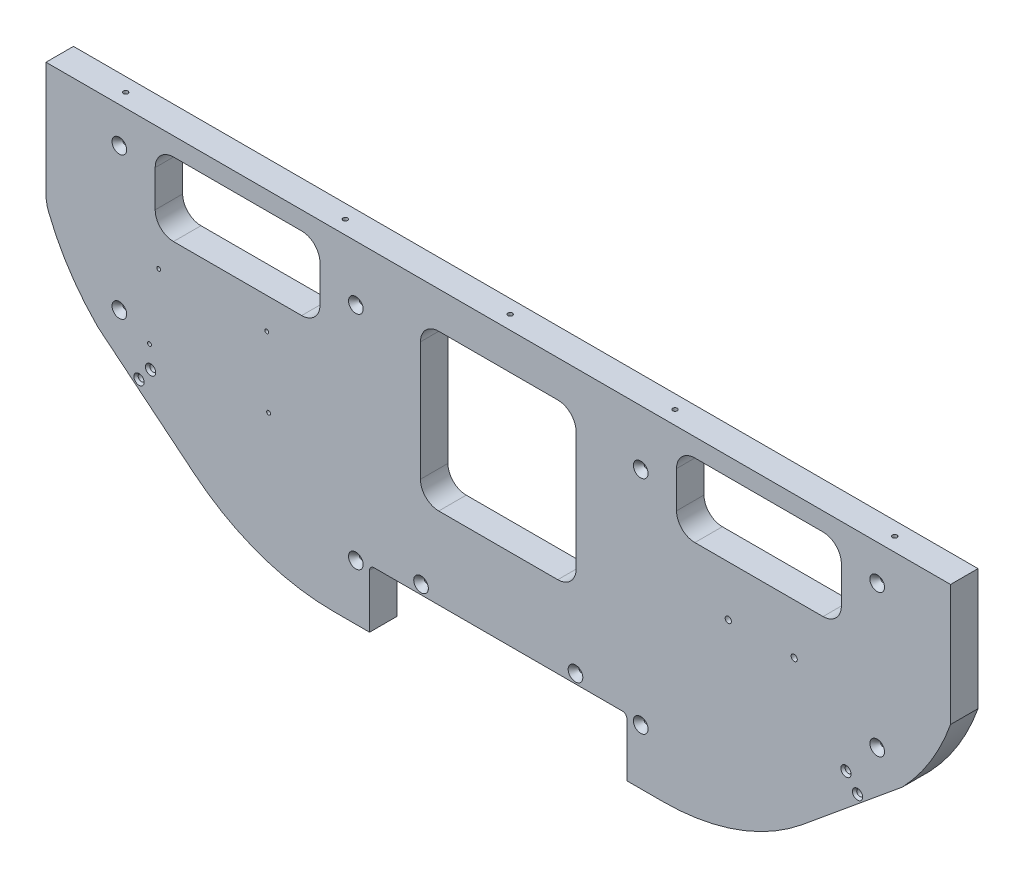
SolidWorks part; units mm, degrees
material "MDF"
ref_plane "Front Plane" through (0, 0, 0) normal (0, 0, 1) x (1, 0, 0)
ref_plane "Top Plane" through (0, 0, 0) normal (0, 1, 0) x (1, 0, 0)
ref_plane "Right Plane" through (0, 0, 0) normal (1, 0, 0) x (0, 0, -1)
sketch "Sketch1" plane through (0, 0, 0) normal (0, 0, 1) x (1, 0, 0)
  line L0 (-394.3668, -87.3125) -> (-394.3668, 23.8125) construction
  line L2 (-618.7885, -233.3625) -> (-593.7568, -233.3625) construction
  line L3 (-394.3668, -87.3125) -> (-394.3668, -3.175)
  line L4 (-497.3744, -199.0142) -> (-427.7551, -141.5981)
  line L5 (-709.3268, -233.3625) -> (-593.7568, -233.3625)
  line L6 (-709.3268, -3.175) -> (-709.3268, -233.3625) construction
  line L7 (-1021.7468, -3.175) -> (-396.9068, -3.175) construction
  line L8 (-394.3668, -3.175) -> (-709.3268, -3.175)
  line L9 (-1021.7468, -3.175) -> (-396.9068, -3.175) construction
  line L10 (-976.0268, -152.2395) -> (-918.7391, -199.0142) construction
  line L11 (-1021.7467, -87.3125) -> (-1021.7467, -20.955) construction
  line L12 (-985.5517, -144.4625) -> (-918.7391, -199.0142)
  line L13 (-1021.7467, -87.3125) -> (-1021.7468, -3.175)
  line L14 (-822.3567, -233.3625) -> (-709.3268, -233.3625)
  line L15 (-709.3268, -3.175) -> (-1021.7468, -3.175)
  arc A0 (-427.7551, -141.5981) -> (-394.3668, -87.3125) centre (-538.0037, -36.3792) ccw construction
  arc A1 (-593.7568, -233.3625) -> (-497.3744, -199.0142) centre (-593.7568, -80.9625) ccw construction
  arc A2 (-427.7551, -141.5981) -> (-394.3668, -87.3125) centre (-538.0037, -36.3792) ccw
  arc A3 (-593.7568, -233.3625) -> (-497.3744, -199.0142) centre (-593.7568, -80.9625) ccw
  arc A4 (-918.7391, -199.0142) -> (-822.3567, -233.3625) centre (-822.3567, -80.9625) ccw construction
  arc A5 (-1021.7467, -87.3125) -> (-985.5517, -144.4625) centre (-878.1098, -36.3792) ccw construction
  arc A6 (-918.7391, -199.0142) -> (-822.3567, -233.3625) centre (-822.3567, -80.9625) ccw
  arc A7 (-1021.7467, -87.3125) -> (-985.5517, -144.4625) centre (-878.1098, -36.3792) ccw
  point P13 (-709.3268, -3.175)
extrude "Boss-Extrude1" add sketch "Sketch1" along normal blind 19.05
hole_wizard "5/64 (0.07813) Diameter Hole1" positions "Sketch2" profile "Sketch3" hole size "5/64" standard "ANSI Inch"
sketch "Sketch2" plane through (-708.0567, 15.875, 6128.5599) normal (0, 1, 0) x (1, 0, 0)
  line L1 (-1.27, 6109.5099) -> (-1.27, 6338.7449) construction
  point P0 (-262.8265, 6157.4524)
  point P6 (-98.7933, 6157.4524)
  point P18 (-262.8265, 6233.6524)
  point P19 (-98.7933, 6233.6524)
  point P22 (-262.8265, 6309.8524)
  point P23 (-98.7933, 6309.8524)
  point P24 (-267.97, 6119.0349)
  point P34 (-115.57, 6119.0349)
  point P37 (-1.27, 6119.0349)
  point P40 (113.03, 6119.0349)
  point P44 (265.43, 6119.0349)
  point P55 (98.7933, 6309.8524)
  point P56 (262.8265, 6309.8524)
  point P59 (98.7933, 6233.6524)
  point P60 (262.8265, 6233.6524)
  point P63 (98.7933, 6157.4524)
  point P64 (262.8265, 6157.4524)
  point P91 (0, 0)
  point P92 (0, 0)
  point P95 (0, 0)
  point P98 (0, 0)
  point P101 (0, 0)
  point P104 (0, 0)
  point P107 (0, 0)
sketch "Sketch3" plane through (-970.8832, 15.875, -28.8925) normal (1, 0, 0) x (0, 0, 1)
  line L0 (0, 0) -> (0, 39.0539)
  line L1 (0, 39.0539) -> (1.5875, 38.1)
  line L2 (1.5875, 38.1) -> (1.5875, 4.0177)
  line L3 (1.5875, 4.0177) -> (5.08, 0)
  line L4 (5.08, 0) -> (0, 0)
  line L5 (-1.5875, 4.0177) -> (-5.08, 0) construction
  line L6 (0, 39.0539) -> (-1.5875, 38.1) construction
  line L7 (0, -6.35) -> (0, 107.95) construction
  dimension "Hole Dia." = 3.175
  dimension "Hole Depth" = 38.1
  dimension "Near C'Sink Dia." = 10.16
  dimension "Near C'Sink Angle" = 82
  dimension "Drill Angle" = 118
hole_wizard "5/64 (0.07813) Diameter Hole2" positions "Sketch4" profile "Sketch5" hole size "5/64" standard "ANSI Inch"
sketch "Sketch4" plane through (-708.0567, 1936.854, 19.05) normal (0, 0, 1) x (-1, 0, 0)
  line L23 (262.8265, 2088.1084) -> (262.8265, 2038.7486)
  line L24 (262.8265, 2038.7486) -> (262.8265, 1989.3888)
  line L25 (262.8265, 1989.3888) -> (262.8265, 2038.7486)
  line L26 (262.8265, 2038.7486) -> (262.8265, 1989.3888)
  line L27 (262.8265, 1989.3888) -> (262.8265, 1940.029)
  line L33 (98.7933, 2170.2165) -> (98.7933, 2131.8519)
  line L35 (98.7933, 2131.8519) -> (98.7933, 2093.4873)
  line L36 (98.7933, 2093.4873) -> (98.7933, 2055.1227)
  line L37 (98.7933, 2055.1227) -> (98.7933, 2016.7581)
  line L38 (98.7933, 2016.7581) -> (98.7933, 1978.3935)
  line L39 (98.7933, 1978.3935) -> (98.7933, 1940.029)
  line L44 (89.2683, 2123.544) -> (53.561, 2123.544)
  line L46 (53.561, 2123.544) -> (17.8537, 2123.544)
  line L47 (17.8537, 2123.544) -> (-17.8537, 2123.544)
  line L48 (-17.8537, 2123.544) -> (-53.561, 2123.544)
  line L49 (-53.561, 2123.544) -> (-89.2683, 2123.544)
  line L53 (0, 2170.2165) -> (-0.3175, 1940.029) construction
  line L55 (-99.3221, 1978.6668) -> (-99.4279, 1940.3024)
  line L56 (-99.2163, 2017.0312) -> (-99.3221, 1978.6668)
  line L57 (-99.1104, 2055.3957) -> (-99.2163, 2017.0312)
  line L58 (-99.0046, 2093.7601) -> (-99.1104, 2055.3957)
  line L59 (-98.8988, 2132.1245) -> (-99.0046, 2093.7601)
  line L60 (-98.7929, 2170.489) -> (-98.8988, 2132.1245)
  line L61 (-263.3243, 1990.1145) -> (-263.4605, 1940.7549)
  line L62 (-263.1882, 2039.4741) -> (-263.3243, 1990.1145)
  line L63 (-263.3243, 1990.1145) -> (-263.1882, 2039.4741)
  line L64 (-263.1882, 2039.4741) -> (-263.3243, 1990.1145)
  line L65 (-263.052, 2088.8338) -> (-263.1882, 2039.4741)
  point P71 (262.8265, 1964.7089)
  point P79 (262.8265, 2063.4285)
  point P95 (98.7933, 2131.8519)
  point P103 (98.7933, 1978.3935)
  point P126 (53.561, 2123.544)
  point P134 (-53.561, 2123.544)
  point P162 (-98.7933, 1978.3935)
  point P166 (-98.7933, 2131.8519)
  point P167 (-262.8265, 2063.4285)
  point P169 (-262.8265, 1964.7089)
  point P184 (0, 0)
  point P185 (0, 0)
  point P186 (0, 0)
  point P189 (0, 0)
  point P192 (0, 0)
  point P195 (0, 0)
sketch "Sketch5" plane through (-445.2302, -27.8549, 19.05) normal (1, 0, 0) x (0, -1, 0)
  line L0 (0, 0) -> (0, 39.0539)
  line L1 (0, 39.0539) -> (1.5875, 38.1)
  line L2 (1.5875, 38.1) -> (1.5875, 4.0177)
  line L3 (1.5875, 4.0177) -> (5.08, 0)
  line L4 (5.08, 0) -> (0, 0)
  line L5 (-1.5875, 4.0177) -> (-5.08, 0) construction
  line L6 (0, 39.0539) -> (-1.5875, 38.1) construction
  line L7 (0, -6.35) -> (0, 107.95) construction
  dimension "Hole Dia." = 3.175
  dimension "Hole Depth" = 38.1
  dimension "Near C'Sink Dia." = 10.16
  dimension "Near C'Sink Angle" = 82
  dimension "Drill Angle" = 118
sketch "Sketch6" plane through (0, 0, 0) normal (0, 0, -1) x (-1, 0, 0)
  line L1 (797.325, -233.3625) -> (618.7884, -233.3625)
  line L2 (797.325, -233.3625) -> (797.325, -193.04)
  line L3 (797.325, -193.04) -> (618.7884, -193.04)
  line L4 (618.7884, -233.3625) -> (618.7884, -193.04)
extrude "Cut-Extrude1" cut sketch "Sketch6" against normal up to next
fillet "Fillet1" radius 25.4 2 edges at (-985.5517, -144.4625, 9.525) (-1021.7467, -87.3125, 9.525)
hole_wizard "#6 Clearance Hole1" positions "Sketch7" profile "Sketch8" hole size "#6" standard "ANSI Inch" end condition up to next
sketch "Sketch7" plane through (0, 0, 19.05) normal (0, 0, 1) x (1, 0, 0)
  arc A0 (-504.7297, -98.0667) -> (-504.7297, -104.8742) centre (-502.7993, -101.4705) ccw construction
  arc A1 (-550.4497, -98.0667) -> (-550.4497, -104.8742) centre (-548.5193, -101.4705) ccw construction
  point P0 (-502.7993, -101.4705)
  point P2 (-548.5193, -101.4705)
sketch "Sketch8" plane through (-502.7993, -101.4705, 19.05) normal (1, 0, 0) x (0, -1, 0)
  line L0 (0, 0) -> (0, 19.05)
  line L1 (0, 19.05) -> (2.1526, 19.05)
  line L2 (2.1526, 19.05) -> (2.1526, 0)
  line L5 (2.1526, 0) -> (0, 0)
  line L11 (0, -6.35) -> (0, 107.95) construction
  dimension "Thru Hole Dia." = 4.3053
  dimension "Thru Hole Depth" = 19.05
hole_wizard "CSK for #6 Flat Head Machine Screw (100)1" positions "Sketch9" profile "Sketch10" countersink size "#6" standard "ANSI Inch" end condition up to next
sketch "Sketch9" plane through (0, 0, 19.05) normal (0, 0, 1) x (1, 0, 0)
  point P0 (-957.2382, -161.4319)
  point P3 (-949.206, -151.5944)
  point P6 (-466.9052, -151.5924)
  point P9 (-458.8731, -161.4298)
sketch "Sketch10" plane through (-957.2382, -161.4319, 19.05) normal (1, 0, 0) x (0, -1, 0)
  line L0 (0, 0) -> (0, 19.05)
  line L1 (0, 19.05) -> (2.1526, 19.05)
  line L2 (2.1526, 19.05) -> (2.1526, 1.5998)
  line L3 (2.1526, 1.5998) -> (3.5433, 0)
  line L5 (3.5433, 0) -> (0, 0)
  line L6 (-2.1526, 1.5998) -> (-3.5433, 0) construction
  line L11 (0, -6.35) -> (0, 107.95) construction
  dimension "Thru Hole Dia." = 4.3053
  dimension "Thru Hole Depth" = 19.05
  dimension "Near C'Sink Dia." = 7.0866
  dimension "Near C'Sink Angle" = 82
sketch "Sketch12" plane through (0, 0, 19.05) normal (0, 0, 1) x (1, 0, 0)
  line L0 (-708.0568, -193.04) -> (-708.0568, -3.175) construction
  line L1 (-797.325, -193.04) -> (-618.7884, -193.04) construction
  line L2 (-394.3668, -3.175) -> (-1021.7468, -3.175) construction
  line L3 (-970.8832, -27.8549) -> (-806.85, -27.8549) construction
  line L4 (-806.85, -41.5396) -> (-806.85, -27.8549) construction
  line L5 (-584.3969, -15.875) -> (-470.0969, -15.875)
  line L6 (-831.7166, -66.675) -> (-946.0166, -66.675)
  line L7 (-831.7166, -66.675) -> (-831.7166, -15.875)
  line L8 (-831.7166, -15.875) -> (-946.0166, -15.875)
  line L9 (-946.0166, -66.675) -> (-946.0166, -15.875)
  line L10 (-831.7166, -66.675) -> (-946.0166, -15.875) construction
  line L11 (-831.7166, -15.875) -> (-946.0166, -66.675) construction
  line L12 (-470.0969, -66.675) -> (-470.0969, -15.875)
  line L13 (-584.3969, -66.675) -> (-470.0969, -66.675)
  line L14 (-584.3969, -66.675) -> (-584.3969, -15.875)
  line L15 (-394.3668, -3.175) -> (-1021.7468, -3.175) construction
  line L16 (-654.0818, -136.525) -> (-762.0318, -136.525)
  line L17 (-654.0818, -136.525) -> (-654.0818, -28.575)
  line L18 (-654.0818, -28.575) -> (-762.0318, -28.575)
  line L19 (-762.0318, -136.525) -> (-762.0318, -28.575)
  line L20 (-654.0818, -136.525) -> (-762.0318, -28.575) construction
  line L21 (-654.0818, -28.575) -> (-762.0318, -136.525) construction
  point P9 (-888.8666, -27.8549)
  point P10 (-888.8666, -41.275)
  point P20 (-708.0568, -82.55)
  dimension "D1" = 114.3
  dimension "D2" = 50.8
  dimension "D3" = 12.7
  dimension "D4" = 107.95
  dimension "D5" = 107.95
  dimension "D6" = 25.4
extrude "Cut-Extrude2" cut sketch "Sketch12" against normal through all
fillet "Fillet2" radius 12.7 12 edges at (-584.3969, -66.675, 9.525) (-584.3969, -15.875, 9.525) (-470.0969, -15.875, 9.525) (-470.0969, -66.675, 9.525) (-654.0818, -136.525, 9.525) (-654.0818, -28.575, 9.525) (-762.0318, -28.575, 9.525) (-762.0318, -136.525, 9.525) (-946.0166, -66.675, 9.525) (-946.0166, -15.875, 9.525) (-831.7166, -15.875, 9.525) (-831.7166, -66.675, 9.525)
fillet "Fillet3" radius 3.175 2 edges at (-618.7884, -193.04, 9.525) (-797.325, -193.04, 9.525)
hole_wizard "#2 Clearance Hole1" positions "Sketch13" profile "Sketch14" hole size "#2" standard "ANSI Inch" end condition up to next
sketch "Sketch13" plane through (0, 0, 0) normal (0, 0, -1) x (-1, 0, 0)
  point P0 (943.5782, -88.265)
  point P3 (868.6482, -88.265)
  point P6 (867.3782, -136.525)
  point P9 (949.9282, -136.525)
sketch "Sketch14" plane through (-943.5782, -88.265, 0) normal (1, 0, 0) x (0, 1, 0)
  line L0 (0, 0) -> (0, 19.05)
  line L1 (0, 19.05) -> (1.3525, 19.05)
  line L2 (1.3525, 19.05) -> (1.3525, 0)
  line L5 (1.3525, 0) -> (0, 0)
  line L11 (0, -6.35) -> (0, 107.95) construction
  dimension "Thru Hole Dia." = 2.7051
  dimension "Thru Hole Depth" = 19.05
